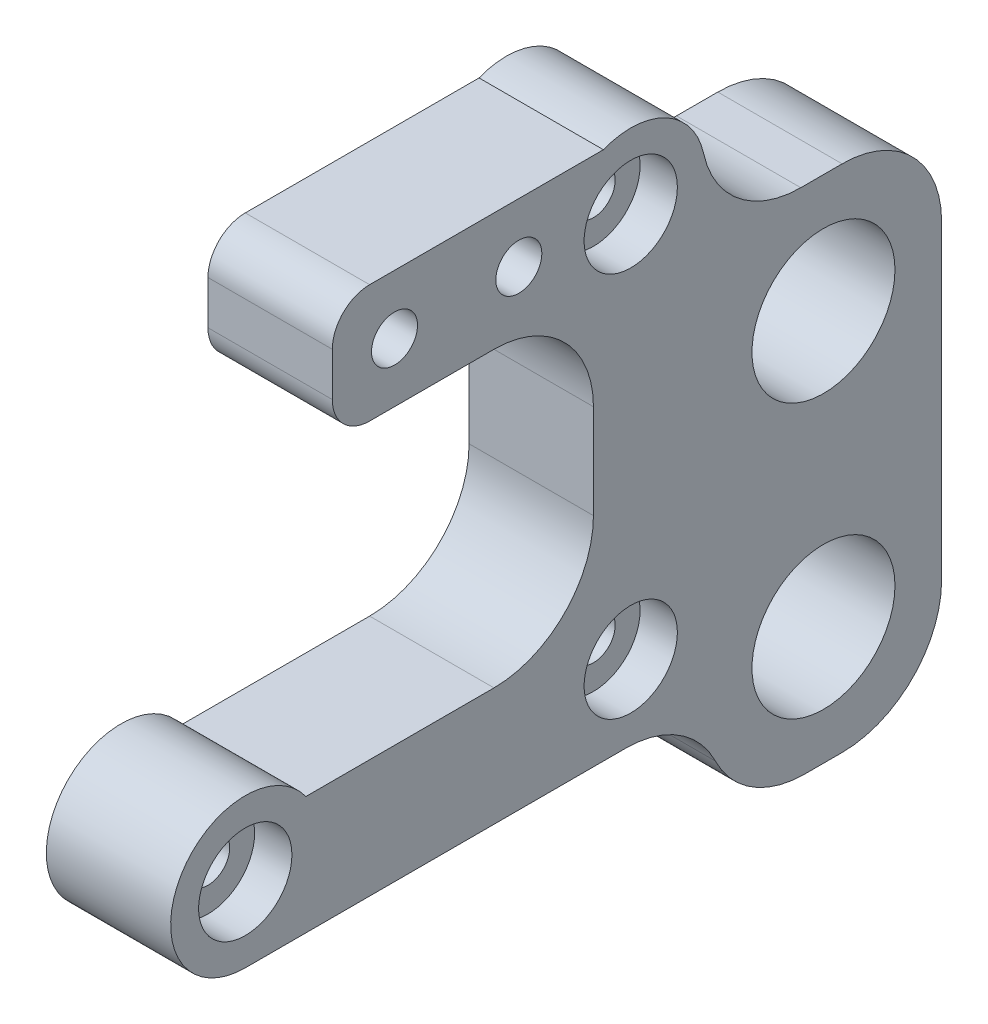
SolidWorks part; units mm, degrees
ref_plane "Front Plane" through (0, 0, 0) normal (0, 0, 1) x (1, 0, 0)
ref_plane "Top Plane" through (0, 0, 0) normal (0, 1, 0) x (1, 0, 0)
ref_plane "Right Plane" through (0, 0, 0) normal (1, 0, 0) x (0, 0, -1)
ref_plane "Plane1" through (20, 0, 0) normal (1, 0, 0) x (0, 0, -1)
sketch "Sketch1" plane through (20, 0, 0) normal (1, 0, 0) x (0, 0, -1)
  line L0 (-17.6996, 42.0822) -> (-39.4998, 42.0822)
  line L1 (-18.4998, 32.5822) -> (-18.4998, 9)
  line L2 (-18.4998, 9) -> (-41.6264, 9)
  line L3 (-46.4998, -0.5) -> (-9.4998, -0.5)
  line L4 (-39.4998, 42.0822) -> (-39.4998, 32.5822)
  line L5 (-9.4998, 36.5) -> (-9.4998, 31.5)
  line L6 (-39.4998, 32.5822) -> (-18.4998, 32.5822)
  line L7 (-9.4998, 31.5) -> (-9.4998, -0.5) construction
  line L8 (9.5002, 31.5) -> (9.5002, -9.5)
  line L9 (9.5002, -9.5) -> (-9.4998, -9.5)
  line L10 (-9.4998, -0.5) -> (-9.4998, -9.5)
  line L13 (-9.4998, 31.5) -> (9.5002, 31.5)
  arc A0 (-41.6264, 9) -> (-46.4998, -0.5) centre (-46.4998, 5.5) ccw
  arc A1 (-9.4998, 36.5) -> (-17.6996, 42.0822) centre (-15.4998, 36.5) ccw
  circle A4 centre (-15.4998, 36.5) radius 1.75
  circle A5 centre (0.0002, 22) radius 5.75
  circle A6 centre (0.0002, 0) radius 5.75
  circle A7 centre (-15.4998, 5.5) radius 1.75
  circle A8 centre (-46.4998, 5.5) radius 1.75
  dimension "D6" = 30
  dimension "D10" = 11.5
  dimension "D18" = 6
  dimension "D19" = 3.5
  dimension "D2" = 31
  dimension "D3" = 31
  dimension "D4" = 41
  dimension "D5" = 9.5
  dimension "D11" = 22
  dimension "D12" = 9.5
  dimension "D13" = 19
  dimension "D14" = 9.5
  dimension "D15" = 9
  dimension "D16" = 9.5
  dimension "D17" = 9
extrude "Boss-Extrude3" add sketch "Sketch1" along normal blind 10
fillet "Fillet1" radius 8 6 edges at (25, -9.5, 9.4998) (25, -9.5, -9.5002) (25, 31.5, -9.5002) (25, 9, 18.4998) (25, 31.5, 9.4998) (25, 32.5822, 18.4998)
sketch "Sketch6" plane through (30, 0, 0) normal (1, 0, 0) x (0, 0, -1)
  circle A0 centre (-15.4998, 36.5) radius 3.75
  circle A1 centre (-15.4998, 5.5) radius 3.75
  circle A2 centre (-46.4998, 5.5) radius 3.75
  dimension "D1" = 7.5
extrude "Cut-Extrude2" cut sketch "Sketch6" against normal blind 3
fillet "Fillet2" radius 8 1 edges at (25, -0.5, 9.4998)
fillet "Fillet3" radius 3 2 edges at (25, 32.5822, 39.4998) (25, 42.0822, 39.4998)
sketch "Sketch8" plane through (30, 0, 0) normal (1, 0, 0) x (0, 0, -1)
  line L2 (-36.4998, 32.5822) -> (-26.4998, 32.5822) construction
  line L3 (-39.4998, 39.0822) -> (-39.4998, 35.5822) construction
  circle A0 centre (-34.4998, 37.3322) radius 1.85
  circle A1 centre (-24.4998, 37.3322) radius 1.85
  dimension "D2" = 3.7
  dimension "D1" = 10
  dimension "D3" = 4.75
  dimension "D4" = 5
extrude "Cut-Extrude3" cut sketch "Sketch8" against normal through all
sketch "Sketch9" plane through (20, 0, 0) normal (-1, 0, 0) x (0, 0, 1)
  circle A0 centre (24.4998, 37.3322) radius 3.75
  circle A1 centre (34.4998, 37.3322) radius 3.75
extrude "Cut-Extrude4" cut sketch "Sketch9" against normal blind 4
